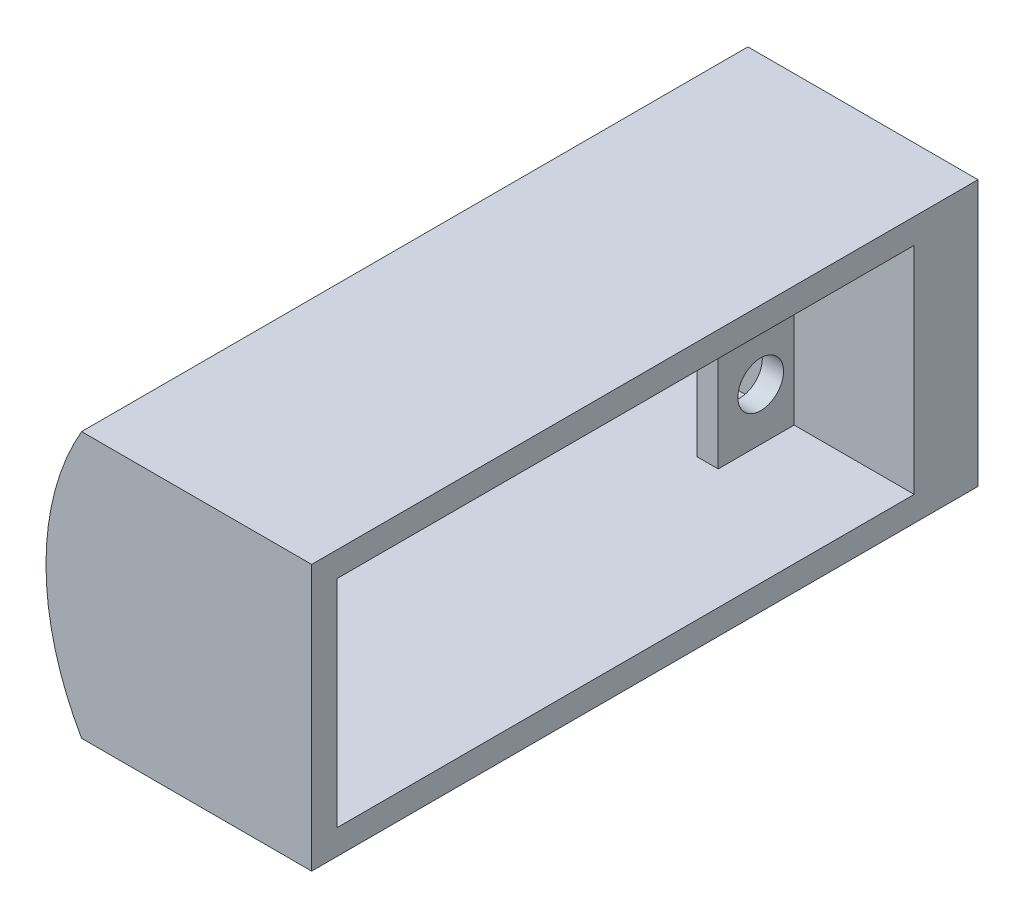
SolidWorks part; units mm, degrees
material "Custom Plastic"
ref_plane "Front Plane" through (0, 0, 0) normal (0, 0, 1) x (1, 0, 0)
ref_plane "Top Plane" through (0, 0, 0) normal (0, 1, 0) x (1, 0, 0)
ref_plane "Right Plane" through (0, 0, 0) normal (1, 0, 0) x (0, 0, -1)
sketch "Sketch1" plane through (0, 0, 0) normal (0, 0, 1) x (1, 0, 0)
  line L0 (-13.75, 13.75) -> (13.75, -13.75) construction
  line L1 (-13.75, 13.75) -> (13.75, 13.75)
  line L2 (-13.75, 13.75) -> (-13.75, -13.75)
  line L3 (-13.75, -13.75) -> (13.75, -13.75)
  line L4 (13.75, 13.75) -> (13.75, -13.75)
  circle A0 centre (0, 0) radius 25
  point P7 (0, 0)
  dimension "D2" = 50
  dimension "2.75" = 27.5
extrude "Boss-Extrude1" add sketch "Sketch1" along normal blind 55
sketch "Sketch2" plane through (0, 0, 0) normal (0, 0, -1) x (-1, 0, 0)
  circle A0 centre (0, 0) radius 25
  circle A1 centre (0, 0) radius 25
  circle A2 centre (0, 0) radius 25
  circle M2 centre (0, 0) radius 25
  line M3 (13.75, 13.75) -> (13.75, -13.75)
  line M4 (13.75, -13.75) -> (-13.75, -13.75)
  line M5 (-13.75, -13.75) -> (-13.75, 13.75)
  line M6 (-13.75, 13.75) -> (13.75, 13.75)
  dimension "D1" = 0
extrude "Boss-Extrude2" add sketch "Sketch2" along normal blind 5 contours M2 M6 M3 M4 M5 | M3 M6 M5 M4 region at (24.2929, 0, 0) region at (0, 0, 0)
sketch "Sketch3" plane through (0, 0, -5) normal (0, 0, -1) x (-1, 0, 0)
  line L1 (0, 25) -> (25, 25)
  line L2 (0, 25) -> (0, -25)
  line L3 (0, -25) -> (25, -25)
  line L4 (25, 25) -> (25, -25)
  circle A0 centre (0, 0) radius 25 construction
extrude "Boss-Extrude3" add sketch "Sketch3" along normal blind 80
ref_plane "Plane1" through (0, 0, -5) normal (0, 0, 1) x (1, 0, 0)
fillet "Fillet1" radius 2.5 4 edges at (-13.75, 13.75, 27.5) (13.75, 13.75, 27.5) (-13.75, -13.75, 27.5) (13.75, -13.75, 27.5)
fillet "Fillet2" radius 2.5 1 edges at (13.75, 0, 55) type face fillet first side face at (25, 0, 55) second side face at (13.75, 0, 27.5) tangent propagation no
ref_plane "Plane2" through (-50, 0, 0) normal (-1, 0, 0) x (0, 0, 1)
sketch "Sketch18" plane through (0, 0, -5) normal (0, 0, 1) x (1, 0, 0)
  line L0 (0, -25) -> (-25, -25)
  line L1 (-25, 0) -> (-25, 25)
  line L2 (-25, -25) -> (0, -25)
  line L3 (-25, 0) -> (-25, -25)
  line L4 (-25, -25) -> (0, -25)
  line L5 (-25, 0) -> (-25, -25)
  line L6 (-25, 25) -> (0, 25)
  arc A1 (-25, 0) -> (0, -25) centre (0, 0) ccw
  arc A2 (-25, 0) -> (0, -25) centre (0, 0) ccw
  circle A3 centre (0, 0) radius 25
  circle A4 centre (0, 0) radius 25
  line M5 (-25, 25) -> (-25, 0)
  arc M6 (-25, 0) -> (0, 25) centre (0, 0) cw
  line M7 (0, 25) -> (-25, 25)
  dimension "D1" = 0
  dimension "D2" = 0
sketch "Sketch21" plane through (0, 0, 0) normal (1, 0, 0) x (0, 0, -1)
  line L0 (24.7, 10.15) -> (79, 10.15)
  line L1 (79, 10.15) -> (79, -10.15)
  line L2 (79, -10.15) -> (24.7, -10.15)
  line L3 (24.7, -10.15) -> (24.7, 10.15)
  line L6 (85, 25) -> (85, -25) construction
  line L7 (51.85, -10.15) -> (51.85, -25)
  line L8 (85, -25) -> (5, -25) construction
  line L9 (51.85, 10.15) -> (51.85, 25)
  line L10 (85, 25) -> (5, 25) construction
  dimension "D1" = 6
  dimension "D2" = 54.3
  dimension "D3" = 20.3
extrude "Cut-Extrude1" cut sketch "Sketch21" against normal blind 11.3 contours L3 L0 L1 L2
sketch "Sketch22" plane through (0, 0, 0) normal (1, 0, 0) x (0, 0, -1)
  line L0 (31.55, 10.15) -> (71.85, 10.15)
  line L1 (24.7, 10.15) -> (79, 10.15) construction
  line L2 (71.85, 10.15) -> (71.85, -10.15)
  line L3 (79, -10.15) -> (24.7, -10.15) construction
  line L4 (71.85, -10.15) -> (31.55, -10.15)
  line L5 (31.55, 10.15) -> (31.55, -10.15)
  line M9 (79, -10.15) -> (24.7, -10.15)
  line M11 (24.7, 10.15) -> (79, 10.15)
  dimension "D1" = 40.3
extrude "Cut-Extrude2" cut sketch "Sketch22" against normal through all contours L5 L2 M11 M9 region at (0, 0, -51.7)
extrude "Cut-Extrude3" cut sketch "Sketch18" against normal through all contours A2 L5 L0 | M7 M5 M6 region at (-19.4158, -19.4158, -5) region at (-19.4158, 19.4158, -5)
sketch "Sketch23" plane through (0, 0, 0) normal (1, 0, 0) x (0, 0, -1)
  line L0 (27.85, 5.25) -> (27.85, -5.25) construction
  line L1 (27.85, -5.25) -> (75.85, -5.25) construction
  line L2 (75.85, -5.25) -> (75.85, 5.25) construction
  line L3 (75.85, 5.25) -> (27.85, 5.25) construction
  circle A0 centre (75.85, 5.25) radius 2.15
  circle A1 centre (75.85, -5.25) radius 2.15
  circle A3 centre (27.85, 5.25) radius 2.15
  circle A4 centre (27.85, -5.25) radius 2.15
  dimension "D1" = 4.3
extrude "Cut-Extrude4" cut sketch "Sketch23" against normal through all contours A4 | A0 | A1 | A3 region at (0, 5.25, -75.85) region at (0, -5.25, -75.85) region at (0, -5.25, -27.85)
ref_plane "Plane3" through (0, 0, -51.7) normal (0, 0, -1) x (-1, 0, 0)
sketch "Sketch24" plane through (0, 0, -51.7) normal (0, 0, -1) x (-1, 0, 0)
  line L0 (13.3, 10.15) -> (13.3, -10.15)
  line L7 (22.8468, 10.15) -> (11.3, 10.15)
  line L8 (11.3, 10.15) -> (11.3, -10.15)
  line L9 (11.3, -10.15) -> (22.8468, -10.15)
  line L13 (22.8468, 10.15) -> (13.3, 10.15)
  line L15 (13.3, -10.15) -> (22.8468, -10.15)
  arc A2 (22.8468, -10.15) -> (22.8468, 10.15) centre (0, 0) ccw
  arc A4 (22.8468, -10.15) -> (22.8468, 10.15) centre (0, 0) ccw
  dimension "D1" = 0
  dimension "D2" = 13.3
extrude "Cut-Extrude7" cut sketch "Sketch24" against normal mid plane 55
sketch "Sketch25" plane through (0, 0, 0) normal (1, 0, 0) x (0, 0, -1)
  line L0 (85, -25) -> (5, -25) construction
  line L1 (-55, 25) -> (22.2914, 25)
  line L2 (-55, 25) -> (-55, -25)
  line L3 (-55, -25) -> (22.2914, -25)
  line L4 (22.2914, 25) -> (22.2914, -25)
extrude "Cut-Extrude8" cut sketch "Sketch25" against normal through all both and the other way through all
sketch "Sketch26" plane through (0, 0, 0) normal (1, 0, 0) x (0, 0, -1)
  line L0 (85, 25) -> (85, -25) construction
  line L1 (22.2914, 25) -> (85, 25)
  line L2 (22.2914, 25) -> (22.2914, 12.5)
  line L3 (22.2914, 12.5) -> (85, 12.5)
  line L4 (85, 25) -> (85, 12.5)
  line L5 (85, -25) -> (22.2914, -25) construction
  line L6 (85, -12.5) -> (22.2914, -12.5)
  line L7 (85, -12.5) -> (85, -25)
  line L8 (85, -25) -> (22.2914, -25)
  line L9 (22.2914, -12.5) -> (22.2914, -25)
  line L10 (22.2914, 25) -> (22.2914, -25) construction
  dimension "D1" = 12.5
extrude "Cut-Extrude9" cut sketch "Sketch26" against normal through all both and the other way through all
